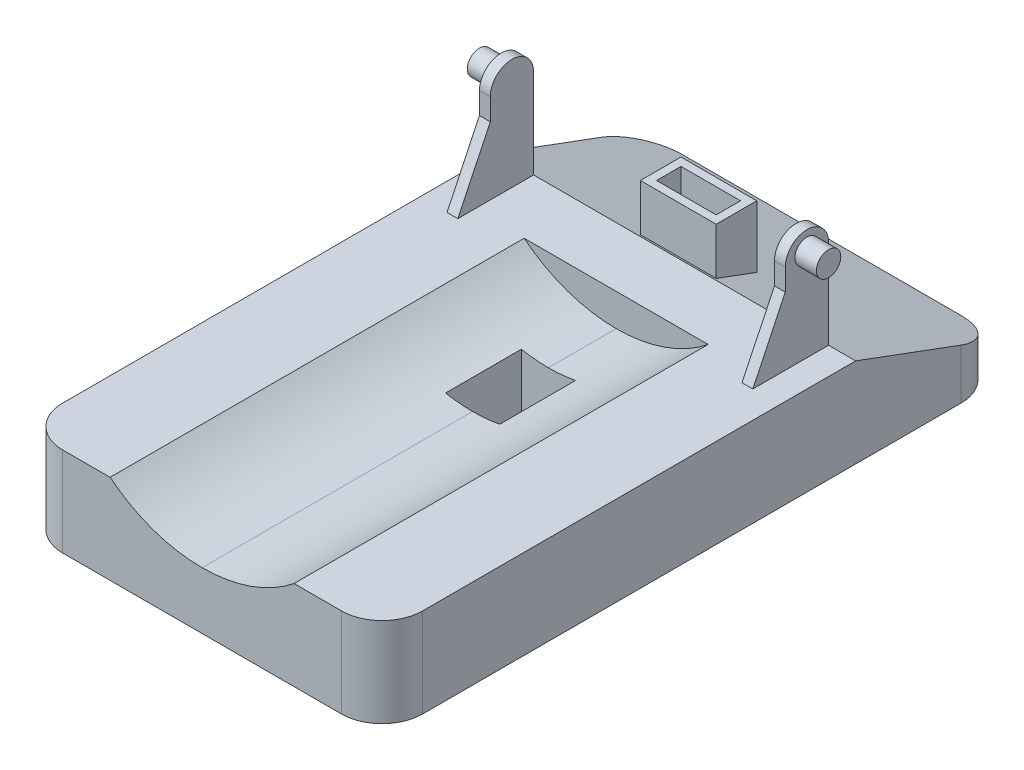
SolidWorks part; units mm, degrees
material "Polyethylene Cross-Linked"
ref_plane "Front Plane" through (0, 0, 0) normal (0, 0, 1) x (1, 0, 0)
ref_plane "Top Plane" through (0, 0, 0) normal (0, 1, 0) x (1, 0, 0)
ref_plane "Right Plane" through (0, 0, 0) normal (1, 0, 0) x (0, 0, -1)
sketch "Sketch1" plane through (0, 0, 0) normal (0, 1, 0) x (1, 0, 0)
  line L0 (0, -7.7913) -> (0, 7.7913) construction
  line L1 (-16.891, 29.083) -> (16.891, 29.083)
  line L2 (-16.891, 29.083) -> (-16.891, -29.083)
  line L3 (-16.891, -29.083) -> (16.891, -29.083)
  line L4 (16.891, 29.083) -> (16.891, -29.083)
  line L5 (-7.7913, 0) -> (7.7913, 0) construction
  point P4 (0, 29.083)
  point P7 (-16.891, 0)
  dimension "D1" = 33.782
  dimension "D2" = 58.166
extrude "Boss-Extrude1" add sketch "Sketch1" along normal blind 8.382
sketch "Sketch2" plane through (0, 0, 29.083) normal (0, 0, 1) x (1, 0, 0)
  line L1 (-16.891, 8.382) -> (16.891, 8.382) construction
  line L2 (0, -10.3378) -> (0, 10.3378) construction
  line L3 (18.5801, 0) -> (-18.5801, 0) construction
  line L4 (-8.636, 8.382) -> (8.636, 8.382)
  arc A0 (-8.636, 8.382) -> (8.636, 8.382) centre (0, 19.0923) ccw
  point P3 (0, 5.334)
  dimension "D1" = 17.272
  dimension "D2" = 5.334
extrude "Cut-Extrude2" cut sketch "Sketch2" against normal blind 38.862
sketch "Sketch3" plane through (16.891, 0, 0) normal (1, 0, 0) x (0, 0, -1)
  line L0 (15.367, 8.382) -> (29.083, 3.302)
  line L1 (-29.083, 8.382) -> (29.083, 8.382) construction
  line L2 (29.083, 8.382) -> (29.083, 0) construction
  line L3 (29.083, 3.302) -> (29.083, 8.382)
  line L4 (29.083, 8.382) -> (15.367, 8.382)
  line L5 (18.5801, 0) -> (-18.5801, 0) construction
  dimension "D1" = 3.302
  dimension "D2" = 13.716
extrude "Cut-Extrude3" cut sketch "Sketch3" against normal through all
sketch "Sketch6" plane through (0, 0, 29.083) normal (0, 0, 1) x (1, 0, 0)
  line L0 (-16.891, 8.382) -> (-8.636, 8.382) construction
  line L9 (18.5801, 0) -> (-18.5801, 0) construction
  line L10 (-16.891, 8.382) -> (-16.891, 0) construction
  line L11 (-3.683, 0) -> (0, 0)
  line L12 (-16.891, 8.382) -> (-8.636, 8.382)
  line L13 (-16.891, 8.382) -> (-16.891, 0)
  line L14 (-16.891, 0) -> (-14.859, 0)
  line L15 (0, 5.3523) -> (0, 0)
  line L16 (0, -10.3378) -> (0, 10.3378) construction
  arc A1 (-3.683, 0) -> (-14.859, 0) centre (-9.271, 0) ccw
  arc A2 (-8.636, 8.382) -> (0, 5.3523) centre (-0.0227, 19.1106) ccw
  dimension "D1" = 7.62
  dimension "D2" = 5.588
  dimension "D3" = 13.7583
  dimension "D4" = 5.3523
shell "Shell1" thickness 1.27 removed face at (0, 0, 0)
sketch "Sketch4" plane through (0, 0, 0) normal (0, -1, 0) x (1, 0, 0)
  line L0 (16.891, -29.083) -> (-16.891, -29.083) construction
  line L1 (-2.667, 1.905) -> (2.413, 1.905)
  line L2 (-2.667, 1.905) -> (-2.667, -4.953)
  line L3 (-2.667, -4.953) -> (2.413, -4.953)
  line L4 (2.413, 1.905) -> (2.413, -4.953)
  line L5 (16.891, 29.083) -> (16.891, -29.083) construction
  dimension "D1" = 24.13
  dimension "D2" = 14.478
  dimension "D3" = 5.08
  dimension "D4" = 6.858
extrude "Cut-Extrude4" cut sketch "Sketch4" against normal through all
extrude "Boss-Extrude3" add sketch "Sketch6" against normal up to vertex (44.2224 mm away) up to point (15.621, 7.112, -15.1394)
mirror "Mirror1" about plane through (0, 0, 0) normal (1, 0, 0) of "Boss-Extrude3"
sketch "Sketch7" plane through (16.891, 0, 0) normal (1, 0, 0) x (0, 0, -1)
  line L0 (15.367, 8.382) -> (15.367, 16.764)
  line L2 (8.255, 8.382) -> (15.367, 8.382)
  line L3 (8.255, 8.382) -> (11.303, 14.732)
  line L4 (11.303, 14.732) -> (11.303, 16.764)
  arc A0 (11.303, 16.764) -> (15.367, 16.764) centre (13.335, 16.764) cw
  point P7 (13.335, 18.796)
  dimension "D1" = 7.112
  dimension "D2" = 8.382
  dimension "D3" = 6.35
  dimension "D4" = 10.414
extrude "Boss-Extrude6" add sketch "Sketch7" against normal blind 1.016 from offset 2.54 offset against normal yes
sketch "Sketch11" plane through (14.351, 0, 0) normal (1, 0, 0) x (0, 0, -1)
  circle A0 centre (13.335, 17.0474) radius 1.143
  dimension "D1" = 2.286
extrude "Boss-Extrude7" add sketch "Sketch11" along normal blind 2.032 contours A0
mirror "Mirror2" about plane through (0, 0, 0) normal (1, 0, 0) of "Boss-Extrude7", "Boss-Extrude6"
ref_plane "Plane2" through (0, 6.35, 0) normal (0, 1, 0) x (1, 0, 0)
sketch "Sketch19" plane through (0, 6.35, 0) normal (0, 1, 0) x (1, 0, 0)
  line L0 (0, -10.3378) -> (0, 10.3378) construction
  line L1 (-3.556, 19.4205) -> (3.556, 19.4205)
  line L2 (-3.556, 19.4205) -> (-3.556, 15.6105)
  line L3 (-3.556, 15.6105) -> (3.556, 15.6105)
  line L4 (3.556, 19.4205) -> (3.556, 15.6105)
  point P4 (0, 19.4205)
  dimension "D1" = 7.112
  dimension "D2" = 3.81
extrude "Boss-Extrude15" add sketch "Sketch19" along normal blind 6.35
sketch "Sketch20" plane through (0, 12.7, 0) normal (0, 1, 0) x (1, 0, 0)
  line L0 (3.556, 19.4205) -> (-3.556, 19.4205) construction
  line L1 (-2.794, 18.6585) -> (2.794, 18.6585)
  line L2 (-2.794, 18.6585) -> (-2.794, 16.3725)
  line L3 (-2.794, 16.3725) -> (2.794, 16.3725)
  line L4 (2.794, 18.6585) -> (2.794, 16.3725)
  line L5 (3.556, 15.6105) -> (3.556, 19.4205) construction
  line L6 (-3.556, 15.6105) -> (3.556, 15.6105) construction
  line L7 (-3.556, 19.4205) -> (-3.556, 15.6105) construction
  dimension "D1" = 0.762
  dimension "D2" = 0.762
  dimension "D3" = 0.762
  dimension "D4" = 0.762
extrude "Cut-Extrude6" cut sketch "Sketch20" against normal through all
sketch "Sketch21" plane through (0, 0, 0) normal (0, -1, 0) x (-1, 0, 0)
  line L1 (2.54, -3.6935) -> (-2.54, -3.6935)
  line L2 (2.54, -3.6935) -> (2.54, 3.4185)
  line L3 (2.54, 3.4185) -> (-2.54, 3.4185)
  line L4 (-2.54, -3.6935) -> (-2.54, 3.4185)
  line L5 (3.556, 15.6105) -> (-3.556, 15.6105) construction
  line L7 (0, 10.3378) -> (0, -10.3378) construction
  point P6 (0, -3.6935)
  dimension "D1" = 5.08
  dimension "D2" = 7.112
  dimension "D3" = 12.192
extrude "Cut-Extrude7" cut sketch "Sketch21" against normal through all
fillet "Fillet1" radius 3.81 4 edges at (16.891, 4.191, 29.083) (-16.891, 4.191, 29.083) (-16.891, 1.651, -29.083) (16.891, 1.651, -29.083)
ref_plane "Plane3" through (0, 3.81, 0) normal (0, 1, 0) x (1, 0, 0)
sketch "Sketch23" plane through (0, 3.81, 0) normal (0, 1, 0) x (1, 0, 0)
  line L0 (0, -10.3378) -> (0, 10.3378) construction
  line L1 (0, 3.4185) -> (2.54, 3.4185) construction
  circle A0 centre (0, 6.2125) radius 1.905
  circle A1 centre (0, 6.2125) radius 0.762
  dimension "D1" = 3.81
  dimension "D2" = 2.794
  dimension "D3" = 1.524
extrude "Cut-Extrude8" cut sketch "Sketch23" against normal blind 6.35 contours A1
sketch "Sketch24" plane through (0, 0, 0) normal (0, -1, 0) x (-1, 0, 0)
  line L0 (0, 10.3378) -> (0, -10.3378) construction
  line L1 (13.081, -29.083) -> (-13.081, -29.083) construction
  circle A0 centre (0, -15.621) radius 1.397
  circle A1 centre (0, -15.621) radius 0.635
  dimension "D1" = 2.794
  dimension "D2" = 1.27
  dimension "D3" = 13.462
extrude "Cut-Extrude10" cut sketch "Sketch24" against normal blind 2.54 contours A1
